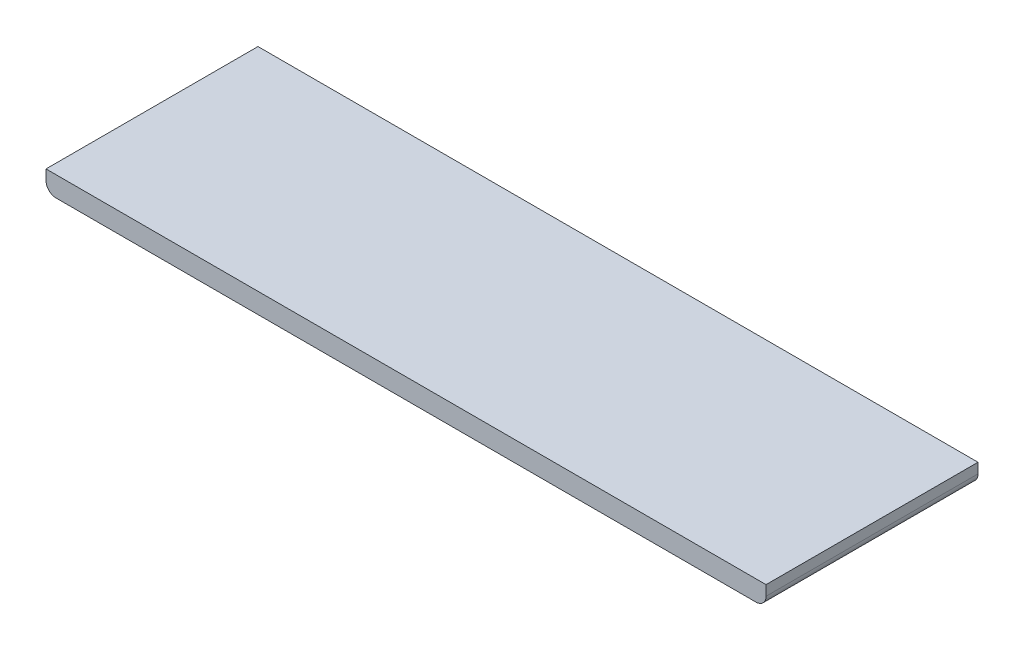
SolidWorks part; units mm, degrees
ref_plane "Спереди" through (0, 0, 0) normal (0, 0, 1) x (1, 0, 0)
ref_plane "Сверху" through (0, 0, 0) normal (0, 1, 0) x (1, 0, 0)
ref_plane "Справа" through (0, 0, 0) normal (1, 0, 0) x (0, 0, -1)
other "Configuration Table"
sketch "Эскиз1" plane through (0, 0, 0) normal (0, 1, 0) x (1, 0, 0)
  line L1 (0, -31.5) -> (107, -31.5)
  line L2 (0, -31.5) -> (0, 0)
  line L3 (0, 0) -> (107, 0)
  line L4 (107, -31.5) -> (107, 0)
extrude "Бобышка-Вытянуть1" add sketch "Эскиз1" along normal blind 3
fillet "tool_D3_R1p5_front_outer_corners" radius 1.5 2 edges at (0, 0, 15.75) (107, 0, 15.75)
